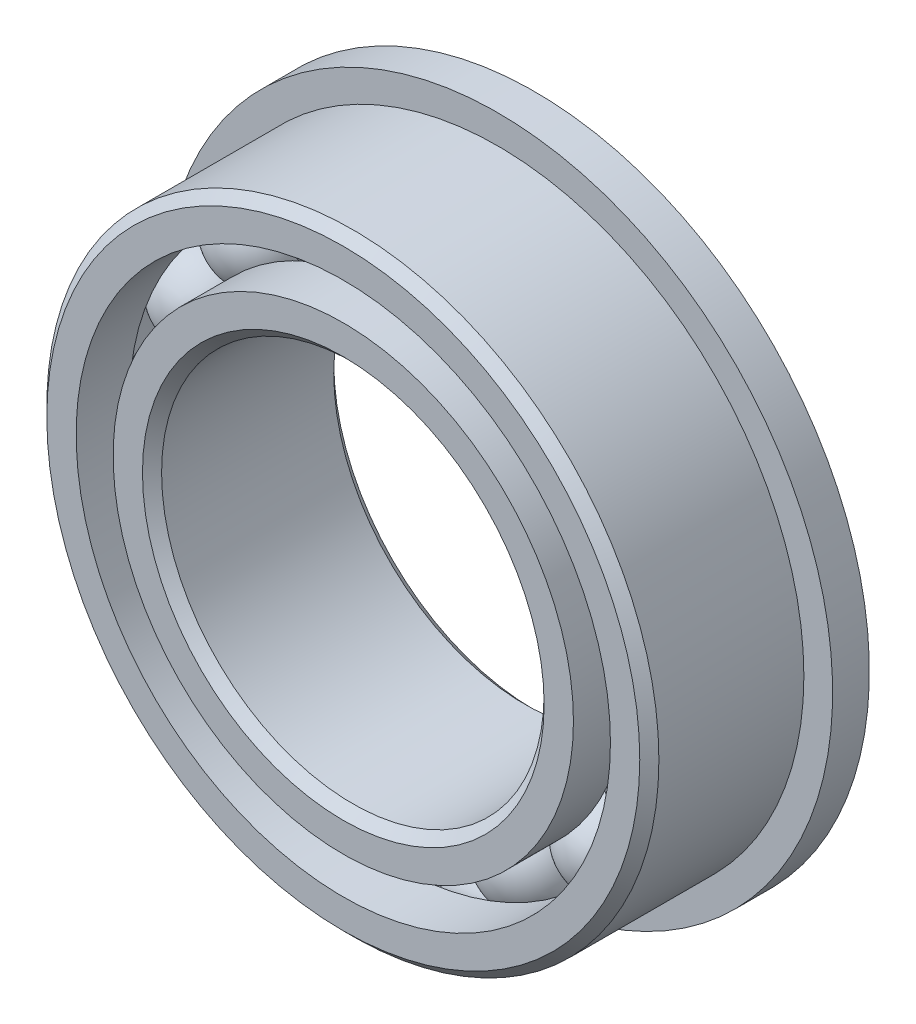
SolidWorks part; units mm, degrees
material "Alloy Steel"
ref_plane "Front Plane" through (0, 0, 0) normal (0, 0, 1) x (1, 0, 0)
ref_plane "Top Plane" through (0, 0, 0) normal (0, 1, 0) x (1, 0, 0)
ref_plane "Right Plane" through (0, 0, 0) normal (1, 0, 0) x (0, 0, -1)
sketch "Sketch1" plane through (0, 0, 0) normal (1, 0, 0) x (0, 0, -1)
  line L0 (-1.9844, 0) -> (1.9844, 0) construction
  line L1 (0, 6.35) -> (0, -6.35) construction
  line L2 (1.7859, 6.35) -> (-1.7859, 6.35)
  line L3 (-1.7859, 6.35) -> (-1.9844, 6.1516)
  line L4 (-1.9844, 6.1516) -> (-1.9844, 5.5432)
  line L5 (-1.9844, 5.5432) -> (-0.8819, 5.5432)
  line L6 (1.9844, 5.5432) -> (0.8819, 5.5432)
  line L7 (1.9844, 6.1516) -> (1.9844, 5.5432)
  line L8 (1.7859, 6.35) -> (1.9844, 6.1516)
  line L9 (0, 6.35) -> (0, 5.1594) construction
  line L10 (0, 5.1594) -> (0, 3.9688) construction
  arc A0 (-0.8819, 5.5432) -> (0.8819, 5.5432) centre (0, 5.1594) cw
  point P14 (0, 3.9688)
  dimension "D3" = 1.7639
  dimension "D1" = 45
  dimension "Width" = 3.9688
  dimension "OD" = 12.7
  dimension "D2" = 0.1984
  dimension "Shaft Dia" = 7.9375
  dimension "D4" = 0.3838
revolve "Revolve1" add sketch "Sketch1" angle 360 about L0
sketch "Sketch3" plane through (0, 0, 0) normal (1, 0, 0) x (0, 0, -1)
  line L0 (-1.7859, 6.35) -> (-1.9844, 6.1516) construction
  line L1 (-0.8819, 4.7756) -> (-1.9844, 4.7756)
  line L2 (-1.9844, 6.1516) -> (-1.9844, 5.5432) construction
  line L3 (-1.9844, 4.7756) -> (-1.9844, 4.1672)
  line L5 (-1.9844, 4.1672) -> (-1.7859, 3.9688)
  line L6 (-1.7859, 3.9688) -> (1.7859, 3.9688)
  line L7 (1.9844, 6.1516) -> (1.9844, 5.5432) construction
  line L8 (1.7859, 3.9688) -> (1.9844, 4.1672)
  line L10 (1.9844, 4.1672) -> (1.9844, 4.7756)
  line L11 (1.9844, 4.7756) -> (0.8819, 4.7756)
  line L13 (1.7859, 6.35) -> (1.9844, 6.1516) construction
  arc A1 (0.8819, 4.7756) -> (-0.8819, 4.7756) centre (0, 5.1594) cw
  arc A2 (0.8819, 5.5432) -> (-0.8819, 5.5432) centre (0, 5.1594) ccw construction
revolve "Revolve3" add sketch "Sketch3" angle 360 about L0
sketch "Sketch5" plane through (0, 0, 0) normal (1, 0, 0) x (0, 0, -1)
  line L0 (1.9844, 6.1516) -> (1.9844, 5.5432) construction
  line L1 (1.9844, 5.8474) -> (1.2224, 5.8474)
  line L2 (1.9844, 5.8474) -> (1.9844, 6.9469)
  line L3 (1.9844, 6.9469) -> (1.2224, 6.9469)
  line L4 (1.2224, 5.8474) -> (1.2224, 6.9469)
  line L5 (1.9844, 0) -> (-1.9844, 0) construction
  dimension "Th" = 0.762
  dimension "Flange OD" = 13.8938
revolve "Revolve5" add sketch "Sketch5" angle 360 about L5
sketch "Sketch4" plane through (0, 0, 0) normal (1, 0, 0) x (0, 0, -1)
  line L0 (-0.9618, 5.1594) -> (0.9618, 5.1594)
  arc A2 (-0.9618, 5.1594) -> (0.9618, 5.1594) centre (0, 5.1594) cw
  arc A3 (0.8819, 5.5432) -> (-0.8819, 5.5432) centre (0, 5.1594) ccw construction
revolve "Revolve4" add sketch "Sketch4" angle 360 about L0
ref_axis "Axis1" through (0, 0, -1.9844) along (0, 0, 1)
pattern_circular "CirPattern1" count 16 every 22.5 about axis through (0, 0, -1.9844) along (0, 0, 1) of bodies 104
equation "\"D2@Sketch1\" = \"Width@Sketch1\"*.05"
equation "\"D3@Sketch1\" = \"Width@Sketch1\"/2.25"
equation "\"D4@Sketch1\" = (((\"OD@Sketch1\"-\"Width@Sketch1\")/2)/3.25)/3.5"
equation "\"D2@CirPattern1\" = 360/\"Balls@CirPattern1\""
